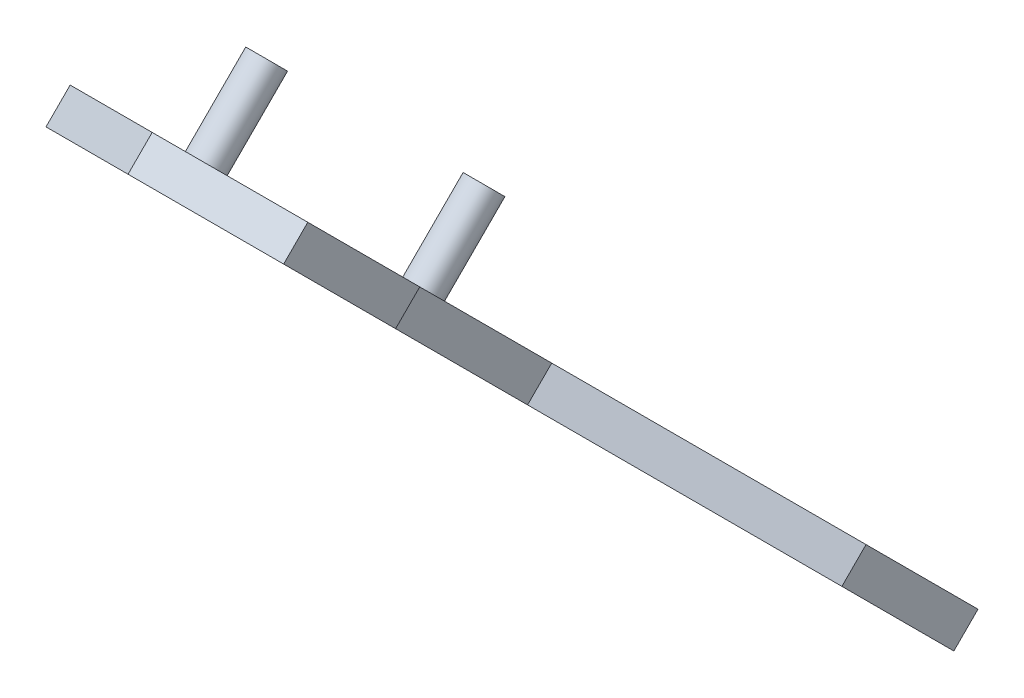
SolidWorks part; units mm, degrees
ref_plane "Plano frontal" through (0, 0, 0) normal (0, 0, 1) x (1, 0, 0)
ref_plane "Plano superior" through (0, 0, 0) normal (0, 1, 0) x (1, 0, 0)
ref_plane "Plano direito" through (0, 0, 0) normal (1, 0, 0) x (0, 0, -1)
sketch "Sketch2" plane through (0, 0, 0) normal (1, 0, 0) x (0, 0, -1)
  line L0 (-40415.6746, 2982.7521) -> (-40415.6746, 3011.0364)
  line L1 (-40415.6746, 3011.0364) -> (-40037.3724, 2632.7343)
  line L2 (-40037.3724, 2632.7343) -> (-40037.3724, 2604.45)
  line L3 (-40037.3724, 2604.45) -> (-40415.6746, 2982.7521)
  line L4 (-40415.6746, 2982.7521) -> (-40429.8167, 2996.8942)
  line L5 (-40293.8504, 2860.928) -> (-40523.5895, 3090.6671) construction
  line L6 (-40429.8167, 2996.8942) -> (-40415.6746, 3011.0364)
  line L7 (-40037.3724, 2632.7343) -> (-40023.2303, 2618.5921)
  line L8 (-40023.2303, 2618.5921) -> (-40037.3724, 2604.45)
  dimension "D1" = 45
  dimension "D2" = 20
extrude "Boss-Extrude1" add sketch "Sketch2" against normal blind 100 and the other way blind 5 from offset 23110 contours L6 L4 L0 | L3 L2 L1 L0 | L8 L7 L2 region at (0, 2996.8942, 40420.3886) region at (0, 2807.7432, 40226.5235) region at (0, 2618.5921, 40032.6584) offset against normal yes
sketch "Sketch3" plane through (0, -18716.4612, 18716.4612) normal (0, -0.7071, 0.7071) x (1, 0, 0)
  line L0 (-23105, 30614.6071) -> (-23105, 30295.3228) construction
  line L1 (-23105, 30707.3218) -> (-22954.8819, 30707.3218)
  line L2 (-23105, 30707.3218) -> (-23105, 30614.6071)
  line L3 (-23105, 30614.6071) -> (-22954.8819, 30614.6071)
  line L4 (-22954.8819, 30707.3218) -> (-22954.8819, 30614.6071)
  line L5 (-23105, 30245.0364) -> (-22954.8819, 30245.0364)
  line L6 (-23105, 30245.0364) -> (-23105, 30152.3218)
  line L7 (-23105, 30152.3218) -> (-22954.8819, 30152.3218)
  line L8 (-22954.8819, 30245.0364) -> (-22954.8819, 30152.3218)
  line L9 (-23105, 30707.3218) -> (-23210, 30707.3218) construction
  line L10 (-23105, 30152.3218) -> (-23210, 30152.3218) construction
extrude "Boss-Extrude2" add sketch "Sketch3" against normal blind 20
sketch "Sketch4" plane through (0, -18702.3191, 18702.3191) normal (0, 0.7071, -0.7071) x (1, 0, 0)
  circle A0 centre (-23146.2304, -30340.7947) radius 10
  circle A2 centre (-23146.2304, -30520.7947) radius 10
  dimension "D1" = 20
  dimension "D2" = 2
extrude "Boss-Extrude3" add sketch "Sketch4" along normal blind 50
ref_plane "Plane1" through (0, -18695.248, 18695.248) normal (0, 0.7071, -0.7071) x (-1, 0, 0)
sketch "Sketch6" plane through (0, -18695.248, 18695.248) normal (0, 0.7071, -0.7071) x (-1, 0, 0)
  point P0 (23146.2304, 30340.7947)
sketch "Sketch7" plane through (0, -18716.4612, 18716.4612) normal (0, -0.7071, 0.7071) x (1, 0, 0)
  line L0 (-22954.8819, 30245.0364) -> (-23105, 30395.1545)
  line L1 (-23210, 30316.3218) -> (-23210, 30152.3218)
  line L2 (-23105, 30245.0364) -> (-23105, 30614.6071) construction
  line L3 (-23210, 30316.3218) -> (-23046, 30152.3218)
  line L4 (-23210, 30152.3218) -> (-23210, 30707.3218) construction
  line L5 (-23210, 30316.3218) -> (-23105, 30395.1545) construction
  line L6 (-23210, 30152.3218) -> (-23046, 30152.3218)
  line L7 (-23210, 30316.3218) -> (-23210, 30543.3218)
  line L8 (-23210, 30543.3218) -> (-23046, 30707.3218)
  line L9 (-23105, 30395.1545) -> (-23105, 30464.4891)
  line L10 (-23105, 30464.4891) -> (-22954.8819, 30614.6071)
  line L11 (-23105, 30464.4891) -> (-23210, 30543.3218) construction
  line L12 (-22954.8819, 30707.3218) -> (-23210, 30707.3218) construction
  line L13 (-22954.8819, 30245.0364) -> (-22954.8819, 30152.3218)
  line L14 (-22954.8819, 30152.3218) -> (-23046, 30152.3218)
  line L15 (-23046, 30707.3218) -> (-22954.8819, 30707.3218)
  line L16 (-22954.8819, 30707.3218) -> (-22954.8819, 30614.6071)
  line L17 (-23210, 30543.3218) -> (-23210, 30707.3218)
  line L18 (-23210, 30707.3218) -> (-23046, 30707.3218)
  line L20 (-22954.8819, 30152.3218) -> (-23210, 30152.3218) construction
  line L21 (-23062.6963, 30506.7928) -> (-23062.6963, 30352.8508)
  point P2 (0, 0)
  line M8 (-22954.8819, 30707.3218) -> (-23210, 30707.3218)
  line M9 (-23210, 30707.3218) -> (-23210, 30152.3218)
  line M12 (-22954.8819, 30245.0364) -> (-23105, 30245.0364)
  line M13 (-23105, 30245.0364) -> (-23105, 30614.6071)
  line M14 (-23105, 30614.6071) -> (-22954.8819, 30614.6071)
  dimension "D1" = 45
  dimension "D2" = 135
extrude "Cut-Extrude1" cut sketch "Sketch7" against normal through all contours L8 M9 M8 | L6 L3 M9 region at (-23155.3333, 2643.1052, 40076.0276) region at (-23155.3333, 2958.2391, 40391.1615)
extrude "Boss-Extrude4" add sketch "Sketch7<3>" against normal blind 20 separate body contours L10 M13 M14 | L0 M12 M13 | L21 L10 L0 M13 region at (-23054.9606, 2705.3923, 40138.3147) region at (-23081.1764, 2800.6721, 40233.5946) region at (-23054.9606, 2895.9519, 40328.8744)
sketch "Sketch7<3>" plane through (0, -18716.4612, 18716.4612) normal (0, -0.7071, 0.7071) x (1, 0, 0) same geometry as "Sketch7"
